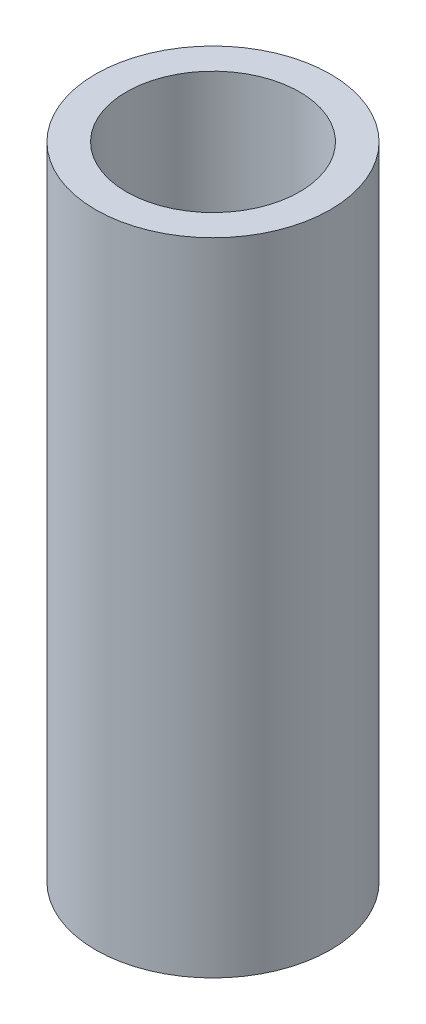
SolidWorks part; units mm, degrees
ref_plane "Front Plane" through (0, 0, 0) normal (0, 0, 1) x (1, 0, 0)
ref_plane "Top Plane" through (0, 0, 0) normal (0, 1, 0) x (1, 0, 0)
ref_plane "Right Plane" through (0, 0, 0) normal (1, 0, 0) x (0, 0, -1)
sketch "Sketch1" plane through (0, 0, 0) normal (0, 1, 0) x (1, 0, 0)
  circle A0 centre (0, 0) radius 17.5
  dimension "SLEEVE_OD" = 35
extrude "Boss-Extrude1" add sketch "Sketch1" along normal blind 95.536
sketch "Sketch2" plane through (0, 0, 0) normal (0, 1, 0) x (1, 0, 0)
  circle A0 centre (0, 0) radius 12.9085
  dimension "BORE_D" = 25.817
extrude "Cut-Extrude1" cut sketch "Sketch2" along normal through all
chamfer "Chamfer1" distance 1.7843 angle 60 rebuild error yes
